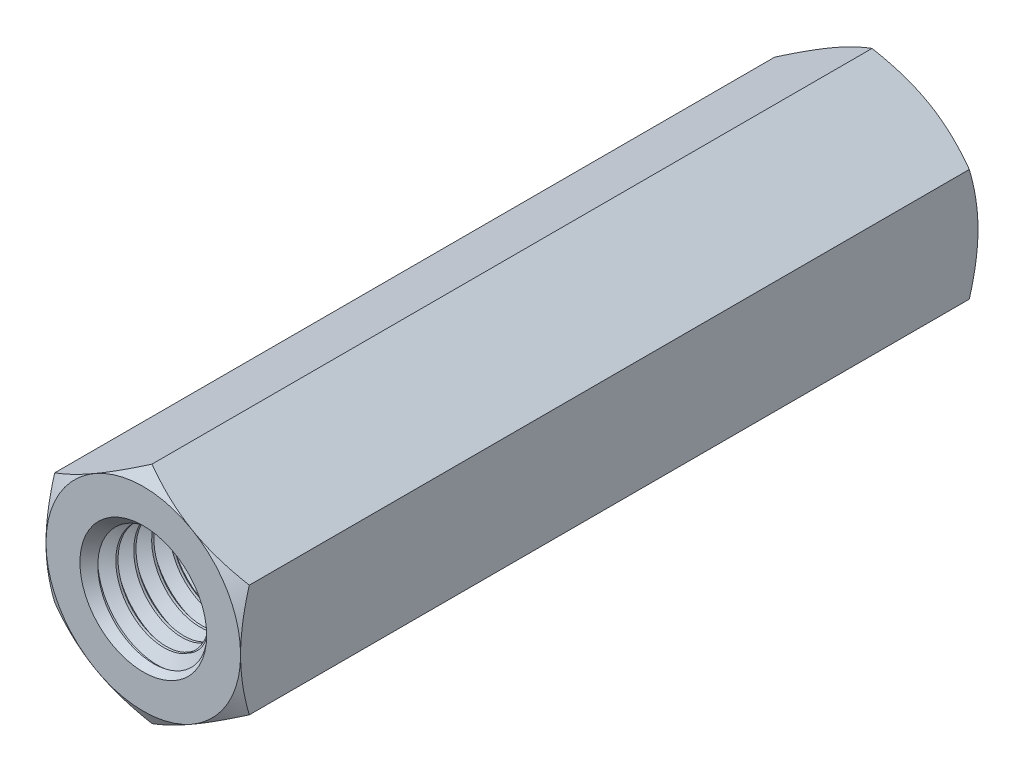
SolidWorks part; units mm, degrees
ref_plane "Front Plane" through (0, 0, 0) normal (0, 0, 1) x (1, 0, 0)
ref_plane "Top Plane" through (0, 0, 0) normal (0, 1, 0) x (1, 0, 0)
ref_plane "Right Plane" through (0, 0, 0) normal (1, 0, 0) x (0, 0, -1)
sketch "Sketch1" plane through (0, 0, 0) normal (1, 0, 0) x (0, 0, -1)
  line L0 (-36, 0) -> (36, 0) construction
  line L1 (-36, 9.5) -> (-36, -9.5) construction
  line L2 (36, 9.5) -> (36, -9.5) construction
  line L3 (0, 0) -> (0, 9.5) construction
  line L4 (-37.6406, 6.1894) -> (-35.8906, 6.1894) construction
  line L5 (-35.8906, 6.1894) -> (-36.7656, 4.6739) construction
  line L6 (-36.7656, 4.6739) -> (-36.7656, 4.8633) construction
  line L7 (-37.6406, 6.1894) -> (-36.7656, 4.6739) construction
  line L8 (-37.5313, 6) -> (-36, 6) construction
  line L9 (-36.875, 4.8633) -> (-36.6563, 4.8633) construction
  line L10 (-36.7656, 6) -> (-36.7656, 6.1894) construction
  line L11 (-37.5859, 6.0947) -> (-35.9453, 6.0947) construction
  point P0 (-36, 6)
  point P4 (0, 0)
  point P8 (-36, 0)
  point P11 (36, 0)
  point P12 (-36, -6)
  point P18 (-20, 0)
  point P23 (-36.7656, 6)
  point P26 (-36.7656, 4.8633)
  point P31 (-36.7656, 6.0947)
  dimension "Length" = 72
  dimension "Hex" = 19
  dimension "Thread OD" = 12
  dimension "Thread Length" = 16
  dimension "D1" = 60
  dimension "Pitch" = 1.75
  dimension "D2" = 0.2188
sketch "Sketch2" plane through (0, 0, 0) normal (0, 0, 1) x (1, 0, 0)
  line L1 (0, 10.9697) -> (-9.5, 5.4848)
  line L2 (-9.5, 5.4848) -> (-9.5, -5.4848)
  line L3 (-9.5, -5.4848) -> (0, -10.9697)
  line L4 (0, -10.9697) -> (9.5, -5.4848)
  line L5 (9.5, -5.4848) -> (9.5, 5.4848)
  line L6 (9.5, 5.4848) -> (0, 10.9697)
  circle A0 centre (0, 0) radius 9.5 construction
extrude "Hex Extrude" add sketch "Sketch2" along normal up to vertex (36 mm away) and the other way up to vertex (36 mm away) up to point (0, 0, 36) other way up to point (0, 0, -36)
sketch "Sketch6" plane through (0, 0, 36) normal (0, 0, 1) x (1, 0, 0)
  circle A0 centre (0, 0) radius 9.5
  circle A1 centre (0, 0) radius 9.5 construction
extrude "Hex Cut" cut sketch "Sketch6" against normal through all draft 60 flip side to cut
sketch "Sketch8" plane through (0, 0, 36) normal (0, 0, 1) x (1, 0, 0)
  circle A0 centre (0, 0) radius 6
extrude "Hex Hole Cut" cut sketch "Sketch8" against normal up to vertex (16 mm away) up to point (0, 0, 20)
sketch "Sketch9" plane through (0, 0, 20) normal (0, 0, 1) x (1, 0, 0)
  circle A1 centre (0, 0) radius 6
  circle A2 centre (0, 0) radius 6
  dimension "D1" = 0
extrude "Hex Hole Taper Cut" cut sketch "Sketch9" against normal through all draft 60
pattern_circular "Hex Cut CirPattern" count 2 over 360 about axis through (0, 0, 0) along (0, 1, 0) of "Hex Cut", "Hex Hole Cut", "Hex Hole Taper Cut"
sketch "Sketch3" plane through (0, 0, 36) normal (0, 0, 1) x (1, 0, 0)
  circle A1 centre (0, 0) radius 6
curve "Helix/Spiral1" pitch 1.75 height 17.75 radius 6 centre (0, 0, 36) axis (0, 0, -1) start towards (0, 1, 0)
sketch "Sketch4" plane through (0, 0, 0) normal (1, 0, 0) x (0, 0, -1)
  line L0 (-37.5859, 6.0947) -> (-36.875, 4.8633)
  line L1 (-36.875, 4.8633) -> (-36.6563, 4.8633)
  line L2 (-36.6563, 4.8633) -> (-35.9453, 6.0947)
  line L3 (-35.9453, 6.0947) -> (-37.5859, 6.0947)
sweep "Sweep1" add profiles "Sketch4" path "Helix/Spiral1"
pattern_circular "CirPattern1" count 2 over 360 about axis through (0, 0, 0) along (0, 1, 0) of "Sweep1"
sketch "Sketch5" plane through (0, 0, 0) normal (1, 0, 0) x (0, 0, -1)
  line L0 (-36, 0) -> (36, 0) construction
  line L1 (-36, 0) -> (36, 0) construction
  line L2 (-20, -6) -> (-20, 6) construction
  line L3 (-36, -6) -> (-36, 6) construction
  line L4 (-36, 9.5) -> (-36, -9.5) construction
  line L5 (-36, 6) -> (-37.5313, 6) construction
  line L7 (-37.6406, 4.6739) -> (-34.1938, 4.6739)
  line L9 (-36, -6) -> (-20, -6) construction
  line L10 (-28, -6) -> (-28, 6) construction
  line L16 (-37.6406, 6.1894) -> (-35.8906, 6.1894) construction
  line L17 (-37.6406, 6.1894) -> (-36, 6.1894)
  line L19 (0, 0) -> (0, 9.5) construction
  line L20 (0, 0) -> (0, 9.5) construction
  line L33 (-37.6406, 6.1894) -> (-37.6406, 4.6739)
  line L34 (-36, 6.1894) -> (-34.1938, 4.6739)
  line L35 (36, 6.1894) -> (34.1938, 4.6739)
  line L36 (37.6406, 4.6739) -> (34.1938, 4.6739)
  line L37 (37.6406, 6.1894) -> (37.6406, 4.6739)
  line L38 (37.6406, 6.1894) -> (36, 6.1894)
  point P6 (-20, 0)
  point P12 (-36, 0)
  dimension "D1" = 40
revolve "Cut-Revolve1" cut sketch "Sketch5" angle 360 about L1
equation "\"D2@Sketch1\"=\"Pitch@Sketch1\"/8"
equation "\"D3@Helix/Spiral1\"=\"Thread Length@Sketch1\" + \"Pitch@Sketch1\""
equation "\"D4@Helix/Spiral1\"=\"Pitch@Sketch1\""
